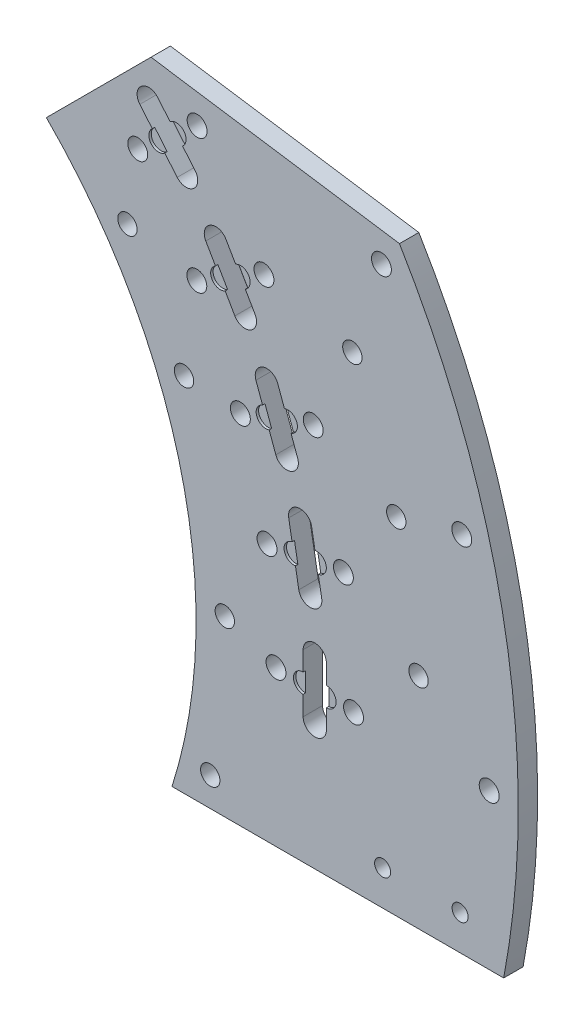
SolidWorks part; units mm, degrees
ref_plane "Front Plane" through (0, 0, 0) normal (0, 0, 1) x (1, 0, 0)
ref_plane "Top Plane" through (0, 0, 0) normal (0, 1, 0) x (1, 0, 0)
ref_plane "Right Plane" through (0, 0, 0) normal (1, 0, 0) x (0, 0, -1)
sketch "Sketch1" plane through (0, 0, 0) normal (0, 0, 1) x (1, 0, 0)
  line L0 (0, 0) -> (177.8, 0) construction
  line L1 (176.8984, 6.1774) -> (0, 0) construction
  line L2 (0, 0) -> (121.7947, 121.7947) construction
  line L3 (121.7947, 121.7947) -> (122.9173, 122.9173) construction
  line L4 (144.995, 101.5266) -> (0, 0) construction
  line L5 (0, 0) -> (163.5325, 67.7374) construction
  line L6 (167.4812, 0) -> (167.4812, -50.8) construction
  line L8 (159.5911, -50.8) -> (167.4812, -50.8) construction
  line L9 (172.1267, -41.275) -> (0, 0) construction
  line L10 (159.5911, -50.8) -> (268.2828, -50.8)
  line L11 (118.4271, 118.4271) -> (152.7152, 152.7152)
  line L12 (177.8, 0) -> (193.675, 0) construction
  line L13 (202.565, 0) -> (210.185, 0) construction
  line L14 (210.185, 0) -> (219.075, 0) construction
  line L15 (193.675, 0) -> (202.565, 0) construction
  line L16 (202.565, 0) -> (202.565, 9.525)
  line L17 (202.565, 0) -> (202.565, -9.525)
  line L18 (210.185, 9.525) -> (210.185, 0)
  line L19 (210.185, 0) -> (210.185, -9.525)
  line L20 (202.565, -9.525) -> (210.185, -9.525) construction
  line L21 (202.565, 9.525) -> (210.185, 9.525) construction
  line L22 (210.185, 9.525) -> (219.075, 0) construction
  line L23 (202.565, 9.525) -> (193.675, 0) construction
  line L24 (199.4876, 35.175) -> (201.1416, 25.7947)
  line L25 (199.4876, 35.175) -> (197.8336, 44.5553)
  line L26 (205.3378, 45.8785) -> (206.9918, 36.4982)
  line L27 (206.9918, 36.4982) -> (208.6458, 27.1179)
  line L28 (190.3488, 69.2813) -> (193.6066, 60.3307)
  line L29 (190.3488, 69.2813) -> (187.0911, 78.2319)
  line L30 (194.2516, 80.8381) -> (197.5093, 71.8875)
  line L31 (197.5093, 71.8875) -> (200.767, 62.9369)
  line L32 (175.4264, 101.2825) -> (180.1889, 93.0336)
  line L33 (175.4264, 101.2825) -> (170.6639, 109.5314)
  line L34 (177.263, 113.3414) -> (182.0255, 105.0925)
  line L35 (182.0255, 105.0925) -> (186.788, 96.8436)
  line L36 (155.1738, 130.2063) -> (161.2963, 122.9097)
  line L37 (155.1738, 130.2063) -> (149.0512, 137.5028)
  line L38 (154.8885, 142.4009) -> (161.0111, 135.1043)
  line L39 (161.0111, 135.1043) -> (167.1336, 127.8077)
  line L40 (0, 0) -> (193.675, 0) construction
  line L41 (0, 0) -> (190.7326, 33.6313) construction
  line L42 (0, 0) -> (254, 0) construction
  line L43 (254, 0) -> (263.525, 0) construction
  line L44 (254.5456, 68.2053) -> (0, 0) construction
  line L45 (152.7152, 152.7152) -> (234.123, 140.5088)
  line L46 (167.8212, 140.8187) -> (228.2193, 131.7625) construction
  line L47 (254.5456, 68.2053) -> (263.746, 70.6705) construction
  line L48 (0, 0) -> (240.3818, 21.0307) construction
  line L49 (0, 0) -> (240.3818, 21.0307) construction
  line L50 (0, 0) -> (233.0779, 62.453) construction
  line L51 (215.9, -50.8) -> (215.9, -25.4) construction
  line L52 (215.9, -25.4) -> (266.7, -25.4) construction
  line L53 (266.7, -25.4) -> (266.7, -50.8) construction
  line L54 (228.6, -39.3506) -> (254, -39.3506) construction
  arc A0 (172.2437, 0) -> (121.7947, 121.7947) centre (0, 0) ccw construction
  arc A1 (173.8312, 0) -> (122.9173, 122.9173) centre (0, 0) ccw construction
  circle A2 centre (176.8984, 6.1774) radius 3.175
  circle A3 centre (144.995, 101.5266) radius 3.175
  circle A4 centre (163.5325, 67.7374) radius 3.175
  arc A5 (167.4812, 0) -> (118.4271, 118.4271) centre (0, 0) ccw
  arc A6 (167.4812, 0) -> (159.5911, -50.8) centre (0, 0) cw
  arc A7 (173.8312, 0) -> (166.2428, -50.8) centre (0, 0) cw construction
  circle A8 centre (172.1267, -41.275) radius 3.175
  circle A9 centre (193.675, 0) radius 9.525 construction
  circle A10 centre (219.075, 0) radius 9.525 construction
  arc A11 (202.565, -9.525) -> (210.185, -9.525) centre (206.375, -9.525) ccw
  arc A12 (202.565, 9.525) -> (210.185, 9.525) centre (206.375, 9.525) cw
  circle A13 centre (193.675, 0) radius 3.2639
  circle A14 centre (219.075, 0) radius 3.2639
  circle A15 centre (215.7468, 38.042) radius 3.2639
  arc A16 (201.1416, 25.7947) -> (208.6458, 27.1179) centre (204.8937, 26.4563) ccw
  arc A17 (197.8336, 44.5553) -> (205.3378, 45.8785) centre (201.5857, 45.2169) cw
  circle A18 centre (190.7326, 33.6313) radius 3.2639
  circle A19 centre (205.8632, 74.9281) radius 3.2639
  arc A20 (193.6066, 60.3307) -> (200.767, 62.9369) centre (197.1868, 61.6338) ccw
  arc A21 (187.0911, 78.2319) -> (194.2516, 80.8381) centre (190.6713, 79.535) cw
  circle A22 centre (181.995, 66.2408) radius 3.2639
  circle A23 centre (189.7245, 109.5375) radius 3.2639
  arc A24 (180.1889, 93.0336) -> (186.788, 96.8436) centre (183.4885, 94.9386) ccw
  arc A25 (170.6639, 109.5314) -> (177.263, 113.3414) centre (173.9635, 111.4364) cw
  circle A26 centre (167.7275, 96.8375) radius 3.2639
  circle A27 centre (167.8212, 140.8187) radius 3.2639
  arc A28 (161.2963, 122.9097) -> (167.1336, 127.8077) centre (164.215, 125.3587) ccw
  arc A29 (149.0512, 137.5028) -> (154.8885, 142.4009) centre (151.9699, 139.9519) cw
  circle A30 centre (148.3637, 124.4919) radius 3.2639
  circle A31 centre (263.525, 0) radius 3.2639
  circle A32 centre (254.5456, 68.2053) radius 3.2639
  circle A33 centre (228.2193, 131.7625) radius 3.2639
  arc A34 (234.123, 140.5088) -> (268.2828, -50.8) centre (0, 0) cw
  circle A36 centre (240.3818, 21.0307) radius 3.175
  circle A37 centre (233.0779, 62.453) radius 3.175
  circle A38 centre (218.6921, 101.9778) radius 3.175
  arc A39 (210.185, 0) -> (203.9537, -50.8) centre (0, 0) cw construction
  circle A40 centre (228.6, -39.3506) radius 2.6289
  circle A41 centre (254, -39.3506) radius 2.6289
  point P3 (172.2437, 0)
  point P96 (0, 0)
  point P114 (266.7, -38.1)
  dimension "D3" = 1.5875
  dimension "D4" = 6.35
  dimension "D5" = 2
  dimension "D7" = 10
  dimension "D8" = 6.35
  dimension "D9" = 6.35
  dimension "D11" = 6.35
  dimension "D13" = 6.35
  dimension "D15" = 19.05
  dimension "D16" = 7.62
  dimension "D17" = 19.05
  dimension "D21" = 15.875
  dimension "D22" = 6.5278
  dimension "D23" = 6.5278
  dimension "D28" = 6.5278
  dimension "D32" = 9.525
  dimension "D33" = 5
  dimension "D34" = 241.3
  dimension "D35" = 6.35
  dimension "D38" = 25.4
  dimension "D40" = 5.2578
  dimension "D41" = 5.2578
  dimension "D43" = 12.7
  dimension "D1" = 177.8
  dimension "D2" = 5.5562
  dimension "D6" = 45
  dimension "D10" = 22.5
  dimension "D12" = 50.8
  dimension "D14" = 9.525
  dimension "D18" = 9.525
  dimension "D19" = 9.525
  dimension "D20" = 25.4
  dimension "D25" = 10
  dimension "D26" = 254
  dimension "D27" = 9.525
  dimension "D30" = 15
  dimension "D31" = 9.525
  dimension "D37" = 10
  dimension "D39" = 50.8
  dimension "D42" = 25.4
  dimension "D44" = 215.9
  dimension "D24" = 5
  dimension "D29" = 3
  dimension "D36" = 3
extrude "Boss-Extrude1" add sketch "Sketch1" along normal blind 6.35 contours A34 L45 L11 A5 A6 L10 A33 A32 A31 A30 A27 A26 A23 A22 A19 A18 A15 A14 A13 A8 A4 A3 A2 L16 A12 L18 L19 A11 L17 L25 A17 L26 region at (207.9014, 48.191, 0)
sketch "Sketch2" plane through (0, 0, 6.35) normal (0, 0, 1) x (1, 0, 0)
  line L0 (202.565, -9.525) -> (202.565, 9.525) construction
  line L1 (210.185, 9.525) -> (210.185, -9.525) construction
  line L2 (0, 0) -> (202.565, 0) construction
  line L3 (0, 0) -> (199.4876, 35.175) construction
  circle A0 centre (202.565, 0) radius 3.175
  circle A1 centre (210.185, 0) radius 3.175
  circle A2 centre (199.4876, 35.175) radius 3.175
  circle A3 centre (206.9918, 36.4982) radius 3.175
  circle A4 centre (190.3488, 69.2813) radius 3.175
  circle A5 centre (197.5093, 71.8875) radius 3.175
  circle A6 centre (175.4264, 101.2825) radius 3.175
  circle A7 centre (182.0255, 105.0925) radius 3.175
  circle A8 centre (155.1738, 130.2063) radius 3.175
  circle A9 centre (161.0111, 135.1043) radius 3.175
  dimension "D1" = 6.35
  dimension "D2" = 6.35
  dimension "D4" = 10
  dimension "D3" = 5
extrude "Cut-Extrude1" cut sketch "Sketch2" against normal blind 0.7937
sketch "Sketch3" plane through (0, 0, 6.35) normal (0, 0, 1) x (1, 0, 0)
  line L0 (0, 0) -> (167.4812, 0) construction
  line L1 (159.5911, -50.8) -> (159.5911, 0) construction
  arc A0 (159.5911, -50.8) -> (118.4271, 118.4271) centre (0, 0) ccw construction
  dimension "D1" = 7.8901
